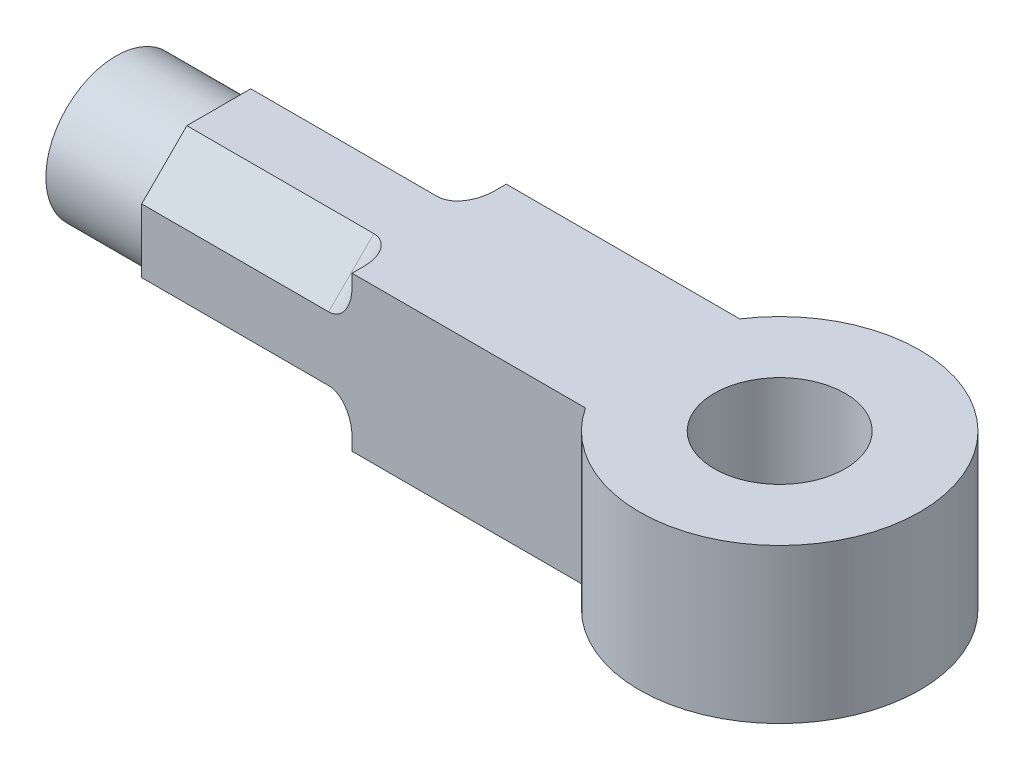
SolidWorks part; units mm, degrees
ref_plane "Front Plane" through (0, 0, 0) normal (0, 0, 1) x (1, 0, 0)
ref_plane "Top Plane" through (0, 0, 0) normal (0, 1, 0) x (1, 0, 0)
ref_plane "Right Plane" through (0, 0, 0) normal (1, 0, 0) x (0, 0, -1)
sketch "Sketch1" plane through (0, 0, 0) normal (0, 1, 0) x (1, 0, 0)
  circle A0 centre (0, 0) radius 14
  circle A1 centre (0, 0) radius 30
  dimension "D1" = 60
  dimension "D2" = 28
extrude "Boss-Extrude1" add sketch "Sketch1" along normal mid plane 36
ref_plane "Plane1" through (-120, 0, 0) normal (1, 0, 0) x (0, 0, -1)
sketch "Sketch2" plane through (-120, 0, 0) normal (1, 0, 0) x (0, 0, -1)
  line L1 (-16.5, 6.8345) -> (-16.5, -6.8345)
  line L2 (-16.5, -6.8345) -> (-6.8345, -16.5)
  line L3 (-6.8345, -16.5) -> (6.8345, -16.5)
  line L4 (6.8345, -16.5) -> (16.5, -6.8345)
  line L5 (16.5, -6.8345) -> (16.5, 6.8345)
  line L6 (16.5, 6.8345) -> (6.8345, 16.5)
  line L7 (6.8345, 16.5) -> (-6.8345, 16.5)
  line L8 (-6.8345, 16.5) -> (-16.5, 6.8345)
  circle A0 centre (0, 0) radius 16.5 construction
extrude "Boss-Extrude2" add sketch "Sketch2" along normal blind 45 separate body
sketch "Sketch3" plane through (-120, 0, 0) normal (1, 0, 0) x (0, 0, -1)
  circle A0 centre (0, 0) radius 15
extrude "Boss-Extrude3" add sketch "Sketch3" against normal blind 22
sketch "Sketch4" plane through (-75, 0, 0) normal (1, 0, 0) x (0, 0, -1)
  line L1 (16.5, 16.5) -> (-16.5, 16.5)
  line L2 (16.5, 16.5) -> (16.5, -16.5)
  line L3 (16.5, -16.5) -> (-16.5, -16.5)
  line L4 (-16.5, 16.5) -> (-16.5, -16.5)
  line L5 (16.5, 16.5) -> (-16.5, -16.5) construction
  line L6 (16.5, -16.5) -> (-16.5, 16.5) construction
  point P0 (0, 0)
  dimension "D1" = 33
  dimension "D2" = 33
extrude "Boss-Extrude4" add sketch "Sketch4" along normal up to next
fillet "Fillet1" radius 5 4 edges at (-75, -11.6673, 11.6673) (-75, -11.6673, -11.6673) (-75, 11.6673, 11.6673) (-75, 11.6673, -11.6673)
fillet "Fillet7" radius 1.5 2 edges at (-30, 16.5, 0) (-30, -16.5, 0)
scale "Scala2" scale about centroid uniform scaling yes scale factor 0.1
sketch "Schizzo1" plane through (0, 1.8, 0) normal (0, 1, 0) x (1, 0, 0)
  line L1 (-47.7552, 5.6069) -> (-33.8168, 5.6069)
  line L2 (-47.7552, 5.6069) -> (-47.7552, -7.1082)
  line L3 (-47.7552, -7.1082) -> (-33.8168, -7.1082)
  line L4 (-33.8168, 5.6069) -> (-33.8168, -7.1082)
extrude "Taglio-Estrusione1" cut sketch "Schizzo1" against normal up to surface (0.15 mm away) up to face at (-49.1803, 1.65, 0)
sketch "Schizzo2" plane through (0, -1.8, 0) normal (0, -1, 0) x (1, 0, 0)
  line L1 (-45.7348, 5.162) -> (-37.0234, 5.162)
  line L2 (-45.7348, 5.162) -> (-45.7348, -5.4215)
  line L3 (-45.7348, -5.4215) -> (-37.0234, -5.4215)
  line L4 (-37.0234, 5.162) -> (-37.0234, -5.4215)
extrude "Taglio-Estrusione2" cut sketch "Schizzo2" against normal up to surface (0.15 mm away) up to face at (-49.1803, -1.65, 0)
